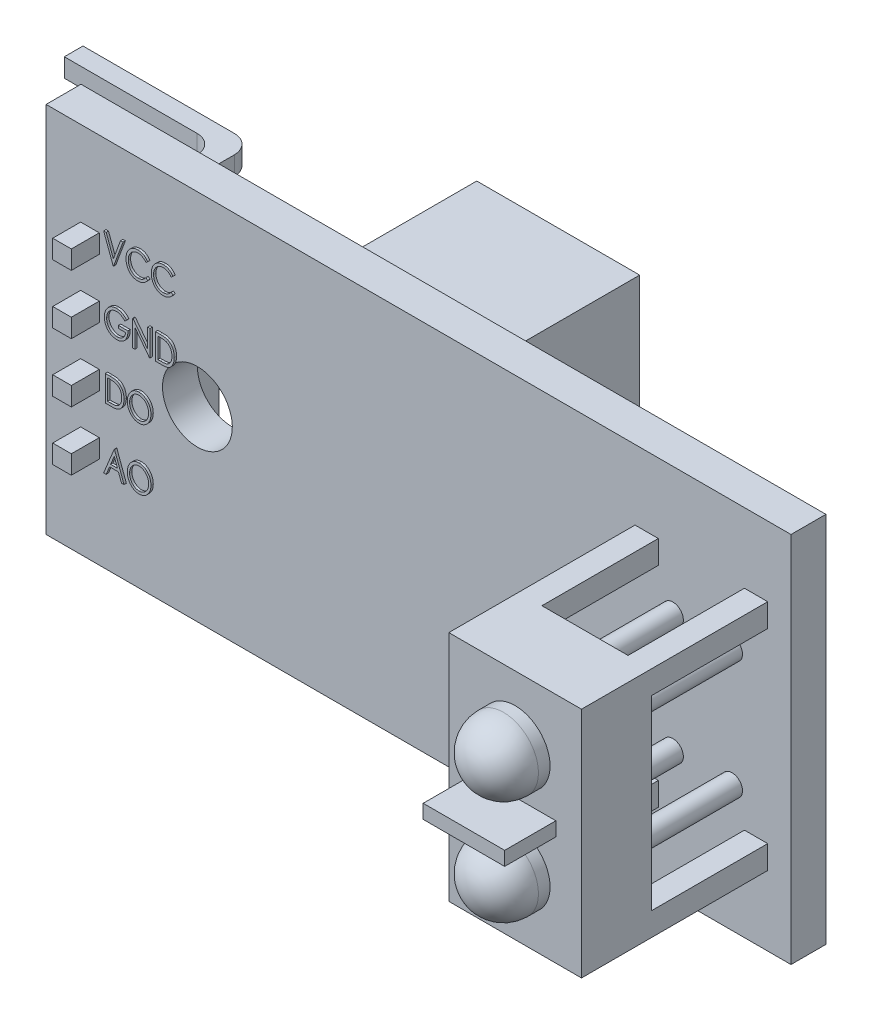
SolidWorks part; units mm, degrees
ref_plane "Спереди" through (0, 0, 0) normal (0, 0, 1) x (1, 0, 0)
ref_plane "Сверху" through (0, 0, 0) normal (0, 1, 0) x (1, 0, 0)
ref_plane "Справа" through (0, 0, 0) normal (1, 0, 0) x (0, 0, -1)
sketch "Эскиз1" plane through (0, 0, 0) normal (0, 0, 1) x (1, 0, 0)
  line L1 (0, 0) -> (32, 0)
  line L2 (0, 0) -> (0, -16)
  line L3 (0, -16) -> (32, -16)
  line L4 (32, 0) -> (32, -16)
  circle A0 centre (6.5, -8) radius 1.5
  point P7 (0, -8)
  dimension "D3" = 3
  dimension "D1" = 32
  dimension "D2" = 16
  dimension "D4" = 6.5
extrude "Бобышка-Вытянуть1" add sketch "Эскиз1" along normal blind 1.5
sketch "Эскиз2" plane through (0, 0, 1.5) normal (0, 0, 1) x (1, 0, 0)
  line L0 (32, -16) -> (32, 0) construction
  line L1 (25.3, -3) -> (31, -3)
  line L2 (25.3, -3) -> (25.3, -13)
  line L3 (25.3, -13) -> (31, -13)
  line L4 (31, -3) -> (31, -13)
  line L6 (25.3, -13) -> (31, -3) construction
  line L7 (31, -13) -> (25.3, -3) construction
  point P4 (32, -8)
  point P5 (31, -8)
  dimension "D1" = 10
  dimension "D2" = 5.7
  dimension "D3" = 1
extrude "Бобышка-Вытянуть2" add sketch "Эскиз2" along normal blind 8
sketch "Эскиз3" plane through (0, 0, 9.5) normal (0, 0, 1) x (1, 0, 0)
  line L0 (31, -3) -> (25.3, -3) construction
  line L1 (26.4, -7.7) -> (29.9, -7.7)
  line L2 (26.4, -7.7) -> (26.4, -8.3)
  line L3 (26.4, -8.3) -> (29.9, -8.3)
  line L4 (29.9, -7.7) -> (29.9, -8.3)
  line L5 (25.3, -3) -> (25.3, -13) construction
  point P4 (28.15, -3)
  point P5 (25.3, -8)
  point P8 (26.4, -8)
  point P11 (28.15, -7.7)
  dimension "D1" = 0.6
  dimension "D2" = 3.5
extrude "Бобышка-Вытянуть3" add sketch "Эскиз3" along normal blind 2.2
sketch "Эскиз4" plane through (0, 0, 9.5) normal (0, 0, 1) x (1, 0, 0)
  line L0 (28.15, -13) -> (28.15, -0.4007) construction
  line L1 (25.3, -13) -> (31, -13) construction
  circle A0 centre (28.15, -5.7911) radius 1.5
  circle A1 centre (28.15, -10.2911) radius 1.5
  dimension "D2" = 3
  dimension "D1" = 4.5
extrude "Бобышка-Вытянуть4" add sketch "Эскиз4" along normal blind 2
fillet "Скругление1" radius 1.5 2 edges at (29.65, -5.7911, 11.5) (29.65, -10.2911, 11.5)
sketch "Эскиз5" plane through (0, -13, 0) normal (0, -1, 0) x (1, 0, 0)
  line L0 (25.3, 1.5) -> (31, 1.5) construction
  line L1 (26.3, 1.5) -> (30, 1.5)
  line L2 (26.3, 1.5) -> (26.3, 6.5)
  line L3 (26.3, 6.5) -> (30, 6.5)
  line L4 (30, 1.5) -> (30, 6.5)
  line L5 (25.3, 9.5) -> (25.3, 1.5) construction
  line L6 (31, 9.5) -> (31, 1.5) construction
  dimension "D1" = 5
  dimension "D2" = 1
  dimension "D3" = 1
extrude "Вырез-Вытянуть1" cut sketch "Эскиз5" against normal through all
sketch "Эскиз7" plane through (31, 0, 0) normal (1, 0, 0) x (0, 0, -1)
  line L0 (-1.5, -13) -> (-1.5, -3) construction
  line L1 (-1.5, -12) -> (-6.5, -12)
  line L2 (-1.5, -12) -> (-1.5, -4)
  line L3 (-1.5, -4) -> (-6.5, -4)
  line L4 (-6.5, -12) -> (-6.5, -4)
  line L5 (-9.5, -13) -> (-1.5, -13) construction
  line L6 (-9.5, -3) -> (-1.5, -3) construction
  dimension "D1" = 5
  dimension "D2" = 1
  dimension "D3" = 1
extrude "Вырез-Вытянуть2" cut sketch "Эскиз7" against normal through all
sketch "Эскиз8" plane through (0, 0, 0) normal (0, 0, -1) x (-1, 0, 0)
  line L1 (-19, 0) -> (-12, 0)
  line L2 (-19, 0) -> (-19, -7)
  line L3 (-19, -7) -> (-12, -7)
  line L4 (-12, 0) -> (-12, -7)
  line L5 (-32, 0) -> (0, 0) construction
  line L6 (0, 0) -> (0, -16) construction
  dimension "D1" = 7
  dimension "D2" = 12
extrude "Бобышка-Вытянуть5" add sketch "Эскиз8" along normal blind 5
sketch "Эскиз9" plane through (0, 0, -5) normal (0, 0, -1) x (-1, 0, 0)
  circle A0 centre (-15.5, -3.5) radius 1.6
  dimension "D1" = 3.2
extrude "Вырез-Вытянуть3" cut sketch "Эскиз9" against normal blind 0.1
sketch "Эскиз10" plane through (0, 0, -4.9) normal (0, 0, -1) x (-1, 0, 0)
  line L0 (-17.0876, -3.3015) -> (-17.0876, -3.6985)
  line L1 (-17.0876, -3.6985) -> (-15.6862, -3.6985)
  line L2 (-15.6862, -5.0891) -> (-15.3015, -5.0891)
  line L3 (-15.6862, -1.9124) -> (-15.6862, -3.3015)
  line L4 (-17.0876, -3.3015) -> (-15.6862, -3.3015)
  line L5 (-15.3015, -1.9124) -> (-15.3015, -3.3015)
  line L6 (-15.6862, -3.6985) -> (-15.6862, -5.0891)
  line L7 (-15.3015, -5.0891) -> (-15.2991, -5.0873)
  line L8 (-15.3015, -3.3015) -> (-13.9124, -3.3015)
  line L9 (-13.9124, -3.6985) -> (-13.9124, -3.3015)
  line L10 (-15.3015, -1.9124) -> (-15.6862, -1.9124)
  line L11 (-15.3015, -3.6985) -> (-15.3015, -5.0891)
  line L14 (-15.3015, -3.6985) -> (-13.9124, -3.6985)
  circle A2 centre (-15.5, -3.5) radius 1.6 construction
  circle A3 centre (-15.5, -3.5) radius 1.6 construction
  circle M1 centre (-15.5, -3.5) radius 1.6
extrude "Вырез-Вытянуть4" cut sketch "Эскиз10" against normal blind 1 contours L11 L14 L9 L8 L5 L10 L3 L4 L0 L1 L6 L2 M1 region at (15.4972, -3.5004, -4.9)
sketch "Эскиз11" plane through (0, 0, 0) normal (0, 0, -1) x (-1, 0, 0)
  line L0 (0, 0) -> (0, -16) construction
  line L1 (-3.135, -3) -> (-0.635, -3)
  line L2 (-3.135, -3) -> (-3.135, -13)
  line L3 (-3.135, -13) -> (-0.635, -13)
  line L4 (-0.635, -3) -> (-0.635, -13)
  point P4 (-0.635, -8)
  point P5 (0, -8)
  dimension "D1" = 10
  dimension "D2" = 2.5
extrude "Бобышка-Вытянуть6" add sketch "Эскиз11" along normal blind 2.8
sketch "Эскиз12" plane through (0, 0, -2.8) normal (0, 0, -1) x (-1, 0, 0)
  line L0 (-1.885, -3) -> (-1.885, -6.4924) construction
  line L1 (-2.285, -3.635) -> (-1.485, -3.635)
  line L2 (-2.285, -3.635) -> (-2.285, -4.435)
  line L3 (-2.285, -4.435) -> (-1.485, -4.435)
  line L4 (-1.485, -3.635) -> (-1.485, -4.435)
  line L5 (-0.635, -3) -> (-3.135, -3) construction
  line L6 (-2.285, -6.175) -> (-1.485, -6.175)
  line L7 (-2.285, -6.175) -> (-2.285, -6.975)
  line L8 (-2.285, -6.975) -> (-1.485, -6.975)
  line L9 (-1.485, -6.175) -> (-1.485, -6.975)
  line L10 (-2.285, -8.715) -> (-1.485, -8.715)
  line L11 (-2.285, -8.715) -> (-2.285, -9.515)
  line L12 (-2.285, -9.515) -> (-1.485, -9.515)
  line L13 (-1.485, -8.715) -> (-1.485, -9.515)
  line L14 (-2.285, -11.255) -> (-1.485, -11.255)
  line L15 (-2.285, -11.255) -> (-2.285, -12.055)
  line L16 (-2.285, -12.055) -> (-1.485, -12.055)
  line L17 (-1.485, -11.255) -> (-1.485, -12.055)
  point P8 (-1.885, -3.635)
  point P15 (-1.885, -6.175)
  point P20 (-1.885, -8.715)
  point P25 (-1.885, -11.255)
  dimension "D1" = 0.8
  dimension "D2" = 0.635
  dimension "D3" = 4
extrude "Бобышка-Вытянуть7" add sketch "Эскиз12" along normal blind 2.3
sketch "Эскиз13" plane through (1.485, 0, 0) normal (-1, 0, 0) x (0, 0, 1)
  line L0 (-5.1, -4.435) -> (-2.8, -4.435) construction
  line L1 (-5.1, -3.635) -> (-4.3, -3.635)
  line L2 (-5.1, -3.635) -> (-5.1, -4.435)
  line L3 (-5.1, -4.435) -> (-4.3, -4.435)
  line L4 (-4.3, -3.635) -> (-4.3, -4.435)
  line L5 (-5.1, -6.175) -> (-4.3, -6.175)
  line L6 (-5.1, -6.175) -> (-5.1, -6.975)
  line L7 (-5.1, -6.975) -> (-4.3, -6.975)
  line L8 (-4.3, -6.175) -> (-4.3, -6.975)
  line L9 (-5.1, -8.715) -> (-4.3, -8.715)
  line L10 (-5.1, -8.715) -> (-5.1, -9.515)
  line L11 (-5.1, -9.515) -> (-4.3, -9.515)
  line L12 (-4.3, -8.715) -> (-4.3, -9.515)
  line L13 (-5.1, -11.255) -> (-4.3, -11.255)
  line L14 (-5.1, -11.255) -> (-5.1, -12.055)
  line L15 (-5.1, -12.055) -> (-4.3, -12.055)
  line L16 (-4.3, -11.255) -> (-4.3, -12.055)
  dimension "D1" = 4
extrude "Бобышка-Вытянуть8" add sketch "Эскиз13" along normal blind 6.5
fillet "Скругление2" radius 0.8 8 edges at (1.485, -4.035, -4.3) (1.485, -6.575, -4.3) (1.485, -9.115, -4.3) (1.485, -11.655, -4.3) (2.285, -11.655, -5.1) (2.285, -9.115, -5.1) (2.285, -6.575, -5.1) (2.285, -4.035, -5.1)
sketch "Эскиз14" plane through (0, 0, 1.5) normal (0, 0, 1) x (1, 0, 0)
  line L0 (1.485, -11.255) -> (2.285, -11.255) construction
  line L1 (1.485, -12.055) -> (2.285, -12.055)
  line L2 (1.485, -12.055) -> (1.485, -11.255)
  line L3 (1.485, -11.255) -> (2.285, -11.255)
  line L4 (2.285, -12.055) -> (2.285, -11.255)
  line L5 (2.285, -11.255) -> (2.285, -12.055) construction
  line L6 (1.485, -9.515) -> (2.285, -9.515)
  line L7 (1.485, -9.515) -> (1.485, -8.715)
  line L8 (1.485, -8.715) -> (2.285, -8.715)
  line L9 (2.285, -9.515) -> (2.285, -8.715)
  line L10 (1.485, -6.975) -> (2.285, -6.975)
  line L11 (1.485, -6.975) -> (1.485, -6.175)
  line L12 (1.485, -6.175) -> (2.285, -6.175)
  line L13 (2.285, -6.975) -> (2.285, -6.175)
  line L14 (1.485, -4.435) -> (2.285, -4.435)
  line L15 (1.485, -4.435) -> (1.485, -3.635)
  line L16 (1.485, -3.635) -> (2.285, -3.635)
  line L17 (2.285, -4.435) -> (2.285, -3.635)
  dimension "D1" = 0.8
  dimension "D2" = 4
extrude "Бобышка-Вытянуть9" add sketch "Эскиз14" along normal blind 1.2
sketch "Эскиз15" plane through (0, 0, 1.5) normal (0, 0, 1) x (1, 0, 0)
  text T0 "VCC\r\nGND\r\nDO\r\nAO" font "Century Gothic" height 1.1
extrude "Бобышка-Вытянуть10" add sketch "Эскиз15" along normal blind 0.1
sketch "Эскиз16" plane through (0, 0, 0) normal (0, 1, 0) x (1, 0, 0)
  line L1 (19, 5) -> (12, 5)
  line L2 (19, 5) -> (19, 0)
  line L3 (19, 0) -> (12, 0)
  line L4 (12, 5) -> (12, 0)
extrude "Вырез-Вытянуть5" cut sketch "Эскиз16" against normal blind 0.1
sketch "Эскиз17" plane through (0, 0, 0) normal (0, 0, -1) x (-1, 0, 0)
  circle A0 centre (-29.4665, -5.4995) radius 0.45
  circle A1 centre (-26.9265, -5.4995) radius 0.45
  circle A2 centre (-29.4665, -10.5795) radius 0.45
  circle A3 centre (-26.9265, -10.5795) radius 0.45
  dimension "D1" = 0.9
  dimension "D2" = 2
  dimension "D3" = 2
extrude "Бобышка-Вытянуть11" add sketch "Эскиз17" along normal blind 0.9 and the other way blind 8
sketch "Эскиз18" plane through (0, 0, 0) normal (0, 0, -1) x (-1, 0, 0)
  line L1 (-17.421, -8.8059) -> (-12.921, -8.8059)
  line L2 (-17.421, -8.8059) -> (-17.421, -14.3059)
  line L3 (-17.421, -14.3059) -> (-12.921, -14.3059)
  line L4 (-12.921, -8.8059) -> (-12.921, -14.3059)
  dimension "D1" = 4.5
  dimension "D2" = 5.5
extrude "Бобышка-Вытянуть12" add sketch "Эскиз18" along normal blind 1.6
sketch "Эскиз19" plane through (0, 0, 0) normal (0, 0, -1) x (-1, 0, 0)
  line L0 (-17.421, -8.8059) -> (-17.421, -14.3059) construction
  line L1 (-19.421, -9.1779) -> (-17.421, -9.1779)
  line L2 (-19.421, -9.1779) -> (-19.421, -9.6779)
  line L3 (-19.421, -9.6779) -> (-17.421, -9.6779)
  line L4 (-17.421, -9.1779) -> (-17.421, -9.6779)
  line L5 (-15.171, -8.8059) -> (-15.171, -17.6918) construction
  line L6 (-12.921, -8.8059) -> (-17.421, -8.8059) construction
  line L7 (-19.421, -10.5843) -> (-17.421, -10.5843)
  line L8 (-19.421, -10.5843) -> (-19.421, -11.0843)
  line L9 (-19.421, -11.0843) -> (-17.421, -11.0843)
  line L10 (-17.421, -10.5843) -> (-17.421, -11.0843)
  line L11 (-19.421, -11.9907) -> (-17.421, -11.9907)
  line L12 (-19.421, -11.9907) -> (-19.421, -12.4907)
  line L13 (-19.421, -12.4907) -> (-17.421, -12.4907)
  line L14 (-17.421, -11.9907) -> (-17.421, -12.4907)
  line L15 (-19.421, -13.3972) -> (-17.421, -13.3972)
  line L16 (-19.421, -13.3972) -> (-19.421, -13.8972)
  line L17 (-19.421, -13.8972) -> (-17.421, -13.8972)
  line L18 (-17.421, -13.3972) -> (-17.421, -13.8972)
  line L19 (-12.921, -13.3972) -> (-12.921, -13.8972)
  line L20 (-10.921, -13.8972) -> (-12.921, -13.8972)
  line L21 (-10.921, -13.3972) -> (-10.921, -13.8972)
  line L22 (-10.921, -13.3972) -> (-12.921, -13.3972)
  line L23 (-12.921, -11.9907) -> (-12.921, -12.4907)
  line L24 (-10.921, -12.4907) -> (-12.921, -12.4907)
  line L25 (-10.921, -11.9907) -> (-10.921, -12.4907)
  line L26 (-10.921, -11.9907) -> (-12.921, -11.9907)
  line L27 (-12.921, -10.5843) -> (-12.921, -11.0843)
  line L28 (-10.921, -11.0843) -> (-12.921, -11.0843)
  line L29 (-10.921, -10.5843) -> (-10.921, -11.0843)
  line L30 (-10.921, -10.5843) -> (-12.921, -10.5843)
  line L31 (-12.921, -9.1779) -> (-12.921, -9.6779)
  line L32 (-10.921, -9.6779) -> (-12.921, -9.6779)
  line L33 (-10.921, -9.1779) -> (-10.921, -9.6779)
  line L34 (-10.921, -9.1779) -> (-12.921, -9.1779)
  dimension "D1" = 0.5
  dimension "D2" = 2
  dimension "D3" = 4
extrude "Бобышка-Вытянуть13" add sketch "Эскиз19" along normal blind 1
chamfer "Фаска1" distance 0.5 angle 50 8 edges at (10.921, -9.4279, -1) (10.921, -10.8343, -1) (10.921, -12.2407, -1) (10.921, -13.6472, -1) (19.421, -9.4279, -1) (19.421, -10.8343, -1) (19.421, -12.2407, -1) (19.421, -13.6472, -1) first distance on face at (10.921, -9.4279, -0.5) first distance on face at (10.921, -10.8343, -0.5) first distance on face at (10.921, -12.2407, -0.5) first distance on face at (10.921, -13.6472, -0.5) first distance on face at (19.421, -9.4279, -0.5) first distance on face at (19.421, -10.8343, -0.5) first distance on face at (19.421, -12.2407, -0.5) first distance on face at (19.421, -13.6472, -0.5)
sketch "Эскиз21" plane through (0, -13.8972, 0) normal (0, -1, 0) x (1, 0, 0)
  line L1 (17.421, 0) -> (18.421, 0)
  line L2 (17.421, 0) -> (17.421, -0.5)
  line L3 (17.421, -0.5) -> (18.421, -0.5)
  line L4 (18.421, 0) -> (18.421, -0.5)
  dimension "D1" = 0.5
  dimension "D2" = 1
extrude "Вырез-Вытянуть6" cut sketch "Эскиз21" against normal blind 5
sketch "Эскиз22" plane through (0, -13.8972, 0) normal (0, -1, 0) x (1, 0, 0)
  line L1 (12.921, 0) -> (11.921, 0)
  line L2 (12.921, 0) -> (12.921, -0.5)
  line L3 (12.921, -0.5) -> (11.921, -0.5)
  line L4 (11.921, 0) -> (11.921, -0.5)
  dimension "D1" = 0.5
  dimension "D2" = 1
extrude "Вырез-Вытянуть7" cut sketch "Эскиз22" against normal blind 5
chamfer "Фаска2" distance 0.5 angle 50 1 edges at (12.921, -11.5559, -1.6) first distance on face at (12.921, -12.2407, -0.75)
sketch "Эскиз23" plane through (0, 0, -1.6) normal (0, 0, -1) x (-1, 0, 0)
  line L0 (-14.7983, -14.3059) -> (-14.7983, -9.7396) construction
  line L1 (-17.421, -14.3059) -> (-13.5168, -14.3059) construction
  text T0 "LM393" font "Century Gothic" height 1
extrude "Вырез-Вытянуть8" cut sketch "Эскиз23" against normal blind 0.1
move or copy body "Body-Move/Copy1" [suppressed] bodies to move or copy 121
